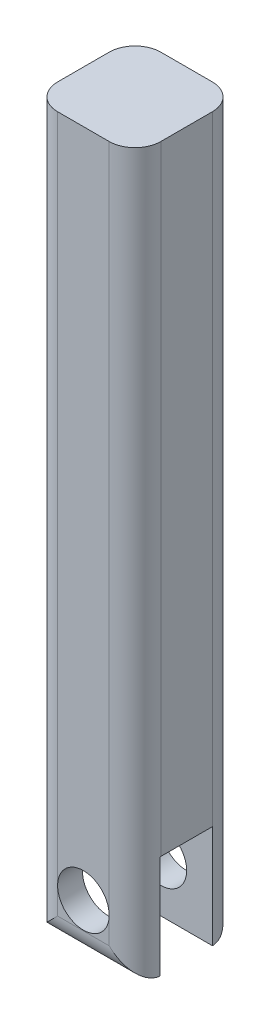
SolidWorks part; units mm, degrees
ref_plane "Front Plane" through (0, 0, 0) normal (0, 0, 1) x (1, 0, 0)
ref_plane "Top Plane" through (0, 0, 0) normal (0, 1, 0) x (1, 0, 0)
ref_plane "Right Plane" through (0, 0, 0) normal (1, 0, 0) x (0, 0, -1)
sketch "Sketch1" plane through (0, 0, 0) normal (0, 1, 0) x (1, 0, 0)
  line L1 (-10, -10) -> (10, -10)
  line L2 (-10, -10) -> (-10, 10)
  line L3 (-10, 10) -> (10, 10)
  line L4 (10, -10) -> (10, 10)
  line L5 (-10, -10) -> (10, 10) construction
  line L6 (-10, 10) -> (10, -10) construction
  point P0 (0, 0)
  dimension "D1" = 20
  dimension "D2" = 20
extrude "Boss-Extrude1" add sketch "Sketch1" along normal blind 140
sketch "Sketch2" plane through (0, 0, 10) normal (0, 0, 1) x (1, 0, 0)
  line L0 (0, -11) -> (0, 11) construction
  circle A0 centre (0, 10.126) radius 5
  dimension "D1" = 10
extrude "Cut-Extrude1" cut sketch "Sketch2" against normal through all
sketch "Sketch3" plane through (10, 0, 0) normal (1, 0, 0) x (0, 0, -1)
  line L0 (11, 0) -> (-11, 0) construction
  line L1 (-5.19, 0) -> (5.01, 0)
  line L2 (-5.19, 0) -> (-5.19, 20)
  line L3 (-5.19, 20) -> (5.01, 20)
  line L4 (5.01, 0) -> (5.01, 20)
  line L5 (0, 11) -> (0, -11) construction
  dimension "D1" = 10.2
  dimension "D2" = 5.01
  dimension "D3" = 20
extrude "Cut-Extrude2" cut sketch "Sketch3" against normal through all
fillet "Fillet1" radius 5 6 edges at (0, 0, -10) (0, 0, 10) (-10, 70, -10) (10, 70, -10) (-10, 70, 10) (10, 70, 10)
